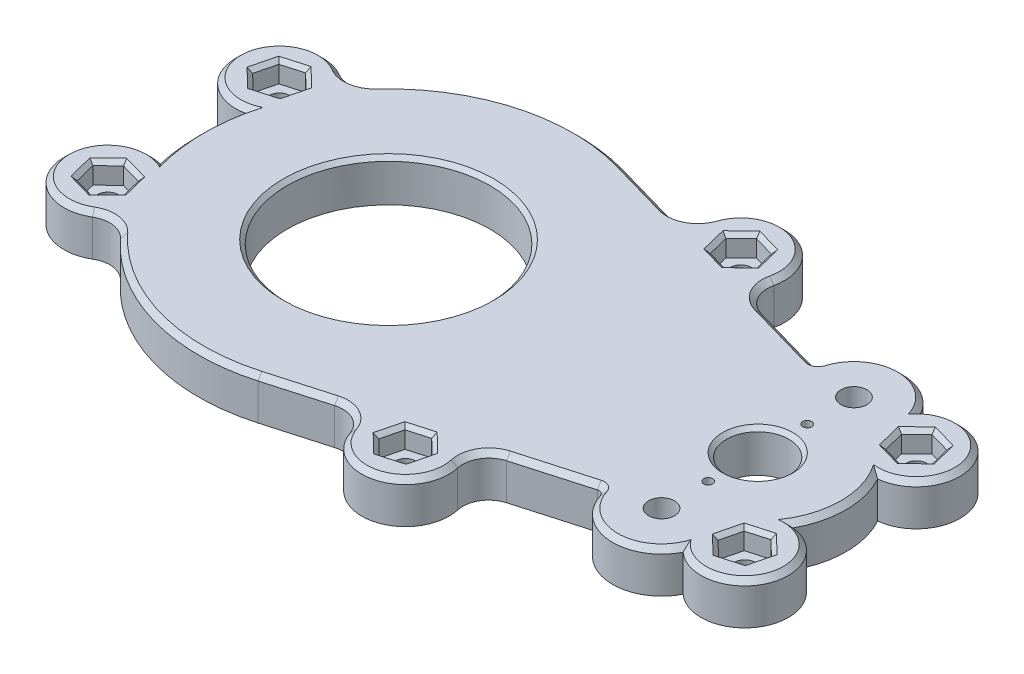
SolidWorks part; units mm, degrees
ref_plane "Front Plane" through (0, 0, 0) normal (0, 0, 1) x (1, 0, 0)
ref_plane "Top Plane" through (0, 0, 0) normal (0, 1, 0) x (1, 0, 0)
ref_plane "Right Plane" through (0, 0, 0) normal (1, 0, 0) x (0, 0, -1)
sketch "Sketch1" plane through (0, 0, 0) normal (0, 1, 0) x (1, 0, 0)
  line L0 (0, 73.0538) -> (0, -65.1274) construction
  line L1 (35.5, 6.365) -> (-28.5632, 24.502) construction
  line L2 (-70.6215, 0) -> (67.3742, 0) construction
  line L3 (35.5, -6.365) -> (-28.5632, -24.502) construction
  line L4 (4.5177, -15.1364) -> (0.1592, 0.2585)
  line L5 (0.1592, 0.2585) -> (4.6815, 1.5388)
  line L6 (4.6815, 1.5388) -> (9.04, -13.8561)
  line L7 (9.04, -13.8561) -> (9.5848, -15.7805)
  line L8 (9.5848, -15.7805) -> (5.0625, -17.0608)
  line L9 (5.0625, -17.0608) -> (4.5177, -15.1364)
  line L10 (-35.5, 0) -> (-60.5, 0) construction
  line L11 (-35.5, 0) -> (-35.5, 25) construction
  line L13 (-100, -75) -> (100, -75)
  line L14 (-100, -75) -> (-100, 75)
  line L15 (-100, 75) -> (100, 75)
  line L16 (100, -75) -> (100, 75)
  line L17 (-100, -75) -> (100, 75) construction
  line L18 (-100, 75) -> (100, -75) construction
  circle A0 centre (35.5, 0) radius 6
  circle A1 centre (-35.5, 0) radius 13.5
  circle A2 centre (-35.5, 0) radius 25.465 construction
  circle A3 centre (35.5, 0) radius 6.365 construction
  circle A4 centre (-60.5, 0) radius 2
  circle A5 centre (-35.5, 25) radius 2
  circle A6 centre (-10.5, 0) radius 2
  circle A7 centre (-35.5, -25) radius 2
  circle A8 centre (35.5, 18.5) radius 2.5
  circle A9 centre (35.5, -18.5) radius 2.5
  point P35 (0, 0)
  dimension "D1" = 12
  dimension "D2" = 27
  dimension "D5" = 50.93
  dimension "D6" = 12.73
  dimension "D12" = 4
  dimension "D19" = 5
  dimension "D3" = 71
  dimension "D4" = 35.5
  dimension "D7" = 90
  dimension "D8" = 27.5
  dimension "D9" = 4.7
  dimension "D10" = 16
  dimension "D11" = 2
  dimension "D13" = 25
  dimension "D15" = 90
  dimension "D16" = 25
  dimension "D17" = 200
  dimension "D18" = 150
  dimension "D20" = 18.5
  dimension "D14" = 4
extrude "Boss-Extrude1" add sketch "Sketch1" along normal blind 4
sketch "Sketch3" plane through (0, 4, 0) normal (0, 1, 0) x (1, 0, 0)
  line L0 (-26.5739, 31.2502) -> (39.0704, 12.5001)
  line L1 (-100, -75) -> (100, -75)
  line L2 (-100, -75) -> (-100, 75)
  line L3 (-100, 75) -> (100, 75)
  line L4 (100, -75) -> (100, 75)
  line L5 (-35.5, 0) -> (35.5, 0) construction
  line L6 (-26.5739, -31.2502) -> (39.0704, -12.5001)
  arc A0 (-26.5739, 31.2502) -> (-26.5739, -31.2502) centre (-35.5, 0) ccw
  arc A1 (39.0704, -12.5001) -> (39.0704, 12.5001) centre (35.5, 0) ccw
  dimension "D1" = 65
  dimension "D2" = 26
extrude "Boss-Extrude2" add sketch "Sketch3" along normal blind 8.25
sketch "Sketch6" plane through (0, 12.25, 0) normal (0, 1, 0) x (1, 0, 0)
  circle A0 centre (35.5, 18.5) radius 5.4
  circle A1 centre (35.5, -18.5) radius 5.4
  dimension "D1" = 10.8
extrude "Cut-Extrude2" cut sketch "Sketch6" against normal up to surface (8.25 mm away) up to face at (-35.5, 4, 27)
fillet "Fillet1" radius 2.5 4 edges at (9.5848, 2, 15.7805) (5.0625, 2, 17.0608) (4.6815, 2, -1.5388) (0.1592, 2, -0.2585)
fillet "Fillet2" radius 5 4 edges at (36.5847, 8.125, 13.2101) (31.7849, 8.125, 14.5811) (36.5847, 8.125, -13.2101) (31.7849, 8.125, -14.5811)
sketch "Sketch2" plane through (0, 4, 0) normal (0, 1, 0) x (1, 0, 0)
  line L0 (29.5, 0) -> (41.5, 0) construction
  line L1 (35.5, 0) -> (35.5, -6) construction
  line L2 (35.5, 0) -> (35.5, 6) construction
  circle A0 centre (-35.5, 25) radius 4.4
  circle A1 centre (-10.5, 0) radius 4.4
  circle A2 centre (-35.5, -25) radius 4.4
  circle A3 centre (-60.5, 0) radius 4.4
  circle A4 centre (35.5, 0) radius 6 construction
  circle A7 centre (35.5, 18.5) radius 5.4
  circle A8 centre (35.5, -18.5) radius 5.4
  arc A9 (40.6003, 16.7261) -> (30.3389, 20.0883) centre (35.5, 18.5) ccw construction
  dimension "D1" = 8.8
extrude "Cut-Extrude1" cut sketch "Sketch2" against normal blind 2
sketch "Sketch8" plane through (0, 0, 0) normal (0, -1, 0) x (1, 0, 0)
  line L0 (-35.5, 0) -> (-100, 0) construction
  line L1 (-100, -75) -> (-100, 75) construction
  line L2 (-35.5, 0) -> (100, 0) construction
  line L3 (100, 75) -> (100, -75) construction
  line L4 (49.5, 21.4955) -> (49.5, -20.5045) construction
  line L5 (0, 32.8542) -> (0, -34.16) construction
  line L6 (-73, 27.0496) -> (-73, -26.9504) construction
  line L11 (-26.5739, -31.2502) -> (24.1868, -16.7513)
  line L12 (24.1868, 16.7513) -> (-26.5739, 31.2502)
  line L13 (-26.5739, -31.2502) -> (24.1868, -16.7513) construction
  line L14 (24.1868, 16.7513) -> (-26.5739, 31.2502) construction
  circle A0 centre (-35.5, 0) radius 32.5 construction
  arc A1 (-26.5739, 31.2502) -> (-26.5739, -31.2502) centre (-35.5, 0) ccw construction
  circle A13 centre (49.5, 16.5) radius 2
  circle A14 centre (-73, 16.5) radius 2
  circle A15 centre (0, 32.25) radius 2
  circle A16 centre (49.5, 16.5) radius 4.4 construction
  circle A17 centre (0, 32.25) radius 4.4 construction
  circle A18 centre (-73, 16.5) radius 4.4 construction
  circle A19 centre (35.5, 18.5) radius 5.4 construction
  arc A20 (40.6003, 16.7261) -> (30.3389, 20.0883) centre (35.5, 18.5) ccw construction
  circle A21 centre (35.5, -18.5) radius 5.4 construction
  circle A22 centre (-73, -16.5) radius 4.4 construction
  circle A23 centre (-73, -16.5) radius 2
  circle A24 centre (0, -32.25) radius 4.4 construction
  circle A25 centre (0, -32.25) radius 2
  circle A26 centre (49.5, -16.5) radius 4.4 construction
  circle A27 centre (49.5, -16.5) radius 2
  circle A28 centre (49.5, 16.5) radius 8.4 construction
  circle A29 centre (0, 32.25) radius 8.4 construction
  circle A30 centre (-73, 16.5) radius 8.4 construction
  arc A44 (30.3389, -20.0883) -> (40.6003, -16.7261) centre (35.5, -18.5) ccw
  arc A45 (42.5943, -10.8936) -> (40.6003, -16.7261) centre (45.3228, -15.0835) ccw
  arc A46 (42.5943, -10.8936) -> (42.5943, 10.8936) centre (35.5, 0) ccw
  arc A47 (40.6003, 16.7261) -> (42.5943, 10.8936) centre (45.3228, 15.0835) ccw
  arc A48 (30.3389, -20.0883) -> (24.1868, -16.7513) centre (25.5601, -21.559) ccw
  arc A49 (40.6003, 16.7261) -> (30.3389, 20.0883) centre (35.5, 18.5) ccw
  arc A50 (24.1868, 16.7513) -> (30.3389, 20.0883) centre (25.5601, 21.559) ccw
  arc A51 (-26.5739, 31.2502) -> (-26.5739, -31.2502) centre (-35.5, 0) ccw
  arc A52 (30.3389, -20.0883) -> (40.6003, -16.7261) centre (35.5, -18.5) ccw construction
  arc A53 (42.5943, -10.8936) -> (40.6003, -16.7261) centre (45.3228, -15.0835) ccw construction
  arc A54 (42.5943, -10.8936) -> (42.5943, 10.8936) centre (35.5, 0) ccw construction
  arc A55 (40.6003, 16.7261) -> (42.5943, 10.8936) centre (45.3228, 15.0835) ccw construction
  arc A56 (30.3389, -20.0883) -> (24.1868, -16.7513) centre (25.5601, -21.559) ccw construction
  arc A57 (40.6003, 16.7261) -> (30.3389, 20.0883) centre (35.5, 18.5) ccw construction
  arc A58 (24.1868, 16.7513) -> (30.3389, 20.0883) centre (25.5601, 21.559) ccw construction
  arc A59 (-26.5739, 31.2502) -> (-26.5739, -31.2502) centre (-35.5, 0) ccw construction
  dimension "D1" = 0
  dimension "D2" = 4
  dimension "D4" = 33
  dimension "D5" = 49.5
  dimension "D3" = 8.8
  dimension "D8" = 16.8
  dimension "D6" = 64.5
  dimension "D7" = 73
extrude "Cut-Extrude3" cut sketch "Sketch8" against normal through all both and the other way through all
sketch "Sketch13" plane through (0, 12.25, 0) normal (0, 1, 0) x (1, 0, 0)
  line L0 (-100, 0) -> (100, 0) construction
  line L1 (-100, 75) -> (-100, -75) construction
  line L2 (100, -75) -> (100, 75) construction
  line L3 (57.9, 16.5) -> (57.9, -16.5) construction
  line L5 (-8.1313, 30.1424) -> (-25.4754, 35.0964)
  line L6 (5.7914, -26.1656) -> (25.2854, -20.5975)
  line L7 (-25.4754, -35.0964) -> (25.2854, -20.5975)
  line L8 (25.2854, 20.5975) -> (-25.4754, 35.0964)
  line L9 (-25.4754, -35.0964) -> (-8.1313, -30.1424)
  line L10 (25.2854, 20.5975) -> (5.7914, 26.1656)
  arc A0 (5.7914, 26.1656) -> (-8.1313, 30.1424) centre (0, 32.25) ccw
  arc A1 (50.4188, 8.1504) -> (43.8854, 22.7479) centre (49.5, 16.5) ccw
  arc A2 (-65.6518, 20.5699) -> (-71.0361, 8.3328) centre (-73, 16.5) ccw
  arc A3 (-65.6518, -20.5699) -> (-71.0361, -8.3328) centre (-73, -16.5) cw
  arc A4 (5.7914, -26.1656) -> (-8.1313, -30.1424) centre (0, -32.25) cw
  arc A5 (50.4188, -8.1504) -> (43.8854, -22.7479) centre (49.5, -16.5) cw
  arc A14 (-71.0361, 8.3328) -> (-71.0361, -8.3328) centre (-35.5, 0) ccw
  arc A15 (-65.6518, -20.5699) -> (-25.4754, -35.0964) centre (-35.5, 0) ccw
  arc A22 (44.3783, 15.412) -> (26.5158, 21.2649) centre (35.5, 18.5) ccw
  arc A23 (44.3783, 15.412) -> (44.7771, 14.2455) centre (45.3228, 15.0835) ccw
  arc A24 (44.7771, -14.2455) -> (44.7771, 14.2455) centre (35.5, 0) ccw
  arc A25 (44.7771, -14.2455) -> (44.3783, -15.412) centre (45.3228, -15.0835) ccw
  arc A26 (26.5158, -21.2649) -> (44.3783, -15.412) centre (35.5, -18.5) ccw
  arc A27 (26.5158, -21.2649) -> (25.2854, -20.5975) centre (25.5601, -21.559) ccw
  arc A28 (-25.4754, 35.0964) -> (-25.4754, -35.0964) centre (-35.5, 0) ccw
  arc A29 (25.2854, 20.5975) -> (26.5158, 21.2649) centre (25.5601, 21.559) ccw
  arc A30 (43.8854, 22.7479) -> (26.5158, 21.2649) centre (35.5, 18.5) ccw
  arc A32 (50.4188, -8.1504) -> (50.4188, 8.1504) centre (35.5, 0) ccw
  arc A34 (26.5158, -21.2649) -> (43.8854, -22.7479) centre (35.5, -18.5) ccw
  arc A35 (26.5158, -21.2649) -> (25.2854, -20.5975) centre (25.5601, -21.559) ccw
  arc A36 (-25.4754, 35.0964) -> (-65.6518, 20.5699) centre (-35.5, 0) ccw
  arc A37 (25.2854, 20.5975) -> (26.5158, 21.2649) centre (25.5601, 21.559) ccw
  dimension "D1" = 16.8
  dimension "D2" = 4
extrude "Cut-Extrude6" cut sketch "Sketch13" against normal through all both and the other way through all flip side to cut
fillet "Fillet4" radius 5 6 edges at (-65.6518, 6.125, 20.5699) (-65.6518, 6.125, -20.5699) (-8.1313, 6.125, -30.1424) (5.7914, 6.125, -26.1656) (5.7914, 6.125, 26.1656) (-8.1313, 6.125, 30.1424)
sketch "Sketch16" plane through (0, 12.25, 0) normal (0, 1, 0) x (1, 0, 0)
  line L12 (-25.4754, -35.0964) -> (-14.035, -31.8287)
  line L13 (11.6951, -24.4793) -> (25.2854, -20.5975)
  line L14 (25.2854, 20.5975) -> (11.6951, 24.4793)
  line L15 (-14.035, 31.8287) -> (-25.4754, 35.0964)
  line L16 (-25.4754, -35.0964) -> (-14.035, -31.8287)
  line L17 (11.6951, -24.4793) -> (25.2854, -20.5975)
  line L18 (25.2854, 20.5975) -> (11.6951, 24.4793)
  line L19 (-14.035, 31.8287) -> (-25.4754, 35.0964)
  arc A60 (-71.0361, 8.3328) -> (-71.0361, -8.3328) centre (-35.5, 0) ccw
  arc A61 (-71.0361, -8.3328) -> (-68.692, -23.7112) centre (-73, -16.5) ccw
  arc A62 (-62.4376, -24.6296) -> (-68.692, -23.7112) centre (-66.1277, -28.0035) ccw
  arc A63 (-62.4376, -24.6296) -> (-25.4754, -35.0964) centre (-35.5, 0) ccw
  arc A64 (-7.9372, -34.9997) -> (-14.035, -31.8287) centre (-12.6617, -36.6364) ccw
  arc A65 (-7.9372, -34.9997) -> (8.1921, -30.3926) centre (0, -32.25) ccw
  arc A66 (11.6951, -24.4793) -> (8.1921, -30.3926) centre (13.0683, -29.2871) ccw
  arc A67 (26.5158, -21.2649) -> (25.2854, -20.5975) centre (25.5601, -21.559) ccw
  arc A68 (26.5158, -21.2649) -> (43.8854, -22.7479) centre (35.5, -18.5) ccw
  arc A69 (43.8854, -22.7479) -> (50.4188, -8.1504) centre (49.5, -16.5) ccw
  arc A70 (50.4188, -8.1504) -> (50.4188, 8.1504) centre (35.5, 0) ccw
  arc A71 (50.4188, 8.1504) -> (43.8854, 22.7479) centre (49.5, 16.5) ccw
  arc A72 (43.8854, 22.7479) -> (26.5158, 21.2649) centre (35.5, 18.5) ccw
  arc A73 (25.2854, 20.5975) -> (26.5158, 21.2649) centre (25.5601, 21.559) ccw
  arc A74 (8.1921, 30.3926) -> (11.6951, 24.4793) centre (13.0683, 29.2871) ccw
  arc A75 (8.1921, 30.3926) -> (-7.9372, 34.9997) centre (0, 32.25) ccw
  arc A76 (-14.035, 31.8287) -> (-7.9372, 34.9997) centre (-12.6617, 36.6364) ccw
  arc A77 (-25.4754, 35.0964) -> (-62.4376, 24.6296) centre (-35.5, 0) ccw
  arc A78 (-68.692, 23.7112) -> (-62.4376, 24.6296) centre (-66.1277, 28.0035) ccw
  arc A79 (-68.692, 23.7112) -> (-71.0361, 8.3328) centre (-73, 16.5) ccw
  arc A80 (-71.0361, 8.3328) -> (-71.0361, -8.3328) centre (-35.5, 0) ccw
  arc A81 (-71.0361, -8.3328) -> (-68.692, -23.7112) centre (-73, -16.5) ccw
  arc A82 (-62.4376, -24.6296) -> (-68.692, -23.7112) centre (-66.1277, -28.0035) ccw
  arc A83 (-62.4376, -24.6296) -> (-25.4754, -35.0964) centre (-35.5, 0) ccw
  arc A84 (-7.9372, -34.9997) -> (-14.035, -31.8287) centre (-12.6617, -36.6364) ccw
  arc A85 (-7.9372, -34.9997) -> (8.1921, -30.3926) centre (0, -32.25) ccw
  arc A86 (11.6951, -24.4793) -> (8.1921, -30.3926) centre (13.0683, -29.2871) ccw
  arc A87 (26.5158, -21.2649) -> (25.2854, -20.5975) centre (25.5601, -21.559) ccw
  arc A88 (26.5158, -21.2649) -> (43.8854, -22.7479) centre (35.5, -18.5) ccw
  arc A89 (43.8854, -22.7479) -> (50.4188, -8.1504) centre (49.5, -16.5) ccw
  arc A90 (50.4188, -8.1504) -> (50.4188, 8.1504) centre (35.5, 0) ccw
  arc A91 (50.4188, 8.1504) -> (43.8854, 22.7479) centre (49.5, 16.5) ccw
  arc A92 (43.8854, 22.7479) -> (26.5158, 21.2649) centre (35.5, 18.5) ccw
  arc A93 (25.2854, 20.5975) -> (26.5158, 21.2649) centre (25.5601, 21.559) ccw
  arc A94 (8.1921, 30.3926) -> (11.6951, 24.4793) centre (13.0683, 29.2871) ccw
  arc A95 (8.1921, 30.3926) -> (-7.9372, 34.9997) centre (0, 32.25) ccw
  arc A96 (-14.035, 31.8287) -> (-7.9372, 34.9997) centre (-12.6617, 36.6364) ccw
  arc A97 (-25.4754, 35.0964) -> (-62.4376, 24.6296) centre (-35.5, 0) ccw
  arc A98 (-68.692, 23.7112) -> (-62.4376, 24.6296) centre (-66.1277, 28.0035) ccw
  arc A99 (-68.692, 23.7112) -> (-71.0361, 8.3328) centre (-73, 16.5) ccw
  dimension "D1" = 0
extrude "Cut-Extrude7" cut sketch "Sketch16" against normal up to surface (10.25 mm away) up to face at (-35.5, 2, -23)
sketch "Sketch17" plane through (0, 0, 0) normal (0, -1, 0) x (1, 0, 0)
  line L4 (4.3815, 14.6553) -> (0.8403, 2.1469)
  line L5 (5.3625, 0.8666) -> (8.9038, 13.375)
  line L6 (4.3815, 14.6553) -> (0.8403, 2.1469)
  line L7 (5.3625, 0.8666) -> (8.9038, 13.375)
  circle A6 centre (-10.5, 0) radius 2
  circle A7 centre (-10.5, 0) radius 2
  arc A8 (2.4216, -0.8943) -> (5.3625, 0.8666) centre (2.9571, 1.5477) ccw
  arc A9 (0.8403, 2.1469) -> (2.4216, -0.8943) centre (3.2457, 1.4659) ccw
  arc A10 (8.9038, 13.375) -> (7.3224, 16.4163) centre (6.4983, 14.056) ccw
  arc A11 (7.3224, 16.4163) -> (4.3815, 14.6553) centre (6.787, 13.9743) ccw
  arc A12 (2.4216, -0.8943) -> (5.3625, 0.8666) centre (2.9571, 1.5477) ccw
  arc A13 (0.8403, 2.1469) -> (2.4216, -0.8943) centre (3.2457, 1.4659) ccw
  arc A14 (8.9038, 13.375) -> (7.3224, 16.4163) centre (6.4983, 14.056) ccw
  arc A15 (7.3224, 16.4163) -> (4.3815, 14.6553) centre (6.787, 13.9743) ccw
  circle A17 centre (-35.5, -25) radius 2
  circle A18 centre (-35.5, -25) radius 2
  circle A20 centre (-35.5, 25) radius 2
  circle A21 centre (-35.5, 25) radius 2
  circle A23 centre (-60.5, 0) radius 2
  circle A24 centre (-60.5, 0) radius 2
  dimension "D1" = 0
  dimension "D2" = 0
  dimension "D3" = 0
  dimension "D4" = 0
  dimension "D5" = 0
extrude "Boss-Extrude3" add sketch "Sketch17" against normal up to surface (2 mm away) up to face at (35.5, 2, -16)
sketch "Sketch18" plane through (0, 2, 0) normal (0, 1, 0) x (1, 0, 0)
  line L8 (-25.4754, -35.0964) -> (-14.035, -31.8287)
  line L9 (11.6951, -24.4793) -> (25.2854, -20.5975)
  line L10 (25.2854, 20.5975) -> (11.6951, 24.4793)
  line L11 (-14.035, 31.8287) -> (-25.4754, 35.0964)
  line L12 (-25.4754, -35.0964) -> (-14.035, -31.8287)
  line L13 (11.6951, -24.4793) -> (25.2854, -20.5975)
  line L14 (25.2854, 20.5975) -> (11.6951, 24.4793)
  line L15 (-14.035, 31.8287) -> (-25.4754, 35.0964)
  circle A20 centre (-35.5, 0) radius 13.5
  circle A21 centre (0, 32.25) radius 2
  circle A22 centre (-73, 16.5) radius 2
  circle A23 centre (-73, -16.5) radius 2
  circle A24 centre (0, 32.25) radius 2 construction
  circle A25 centre (-35.5, 0) radius 13.5 construction
  circle A26 centre (0, -32.25) radius 2
  circle A27 centre (35.5, -18.5) radius 2.5
  circle A28 centre (35.5, 0) radius 6
  circle A29 centre (49.5, -16.5) radius 2
  circle A30 centre (35.5, 18.5) radius 2.5
  circle A31 centre (49.5, 16.5) radius 2
  circle A32 centre (-73, 16.5) radius 2 construction
  circle A33 centre (-73, -16.5) radius 2 construction
  circle A34 centre (0, -32.25) radius 2 construction
  circle A35 centre (35.5, -18.5) radius 2.5 construction
  circle A36 centre (35.5, 0) radius 6 construction
  circle A37 centre (35.5, 18.5) radius 2.5 construction
  circle A38 centre (49.5, 16.5) radius 2 construction
  circle A39 centre (49.5, -16.5) radius 2 construction
  arc A40 (-68.692, 23.7112) -> (-71.0361, 8.3328) centre (-73, 16.5) ccw
  arc A41 (-71.0361, 8.3328) -> (-71.0361, -8.3328) centre (-35.5, 0) ccw
  arc A42 (-71.0361, -8.3328) -> (-68.692, -23.7112) centre (-73, -16.5) ccw
  arc A43 (-62.4376, -24.6296) -> (-68.692, -23.7112) centre (-66.1277, -28.0035) ccw
  arc A44 (-62.4376, -24.6296) -> (-25.4754, -35.0964) centre (-35.5, 0) ccw
  arc A45 (-7.9372, -34.9997) -> (-14.035, -31.8287) centre (-12.6617, -36.6364) ccw
  arc A46 (-7.9372, -34.9997) -> (8.1921, -30.3926) centre (0, -32.25) ccw
  arc A47 (11.6951, -24.4793) -> (8.1921, -30.3926) centre (13.0683, -29.2871) ccw
  arc A48 (26.5158, -21.2649) -> (25.2854, -20.5975) centre (25.5601, -21.559) ccw
  arc A49 (26.5158, -21.2649) -> (43.8854, -22.7479) centre (35.5, -18.5) ccw
  arc A50 (43.8854, -22.7479) -> (50.4188, -8.1504) centre (49.5, -16.5) ccw
  arc A51 (50.4188, -8.1504) -> (50.4188, 8.1504) centre (35.5, 0) ccw
  arc A52 (50.4188, 8.1504) -> (43.8854, 22.7479) centre (49.5, 16.5) ccw
  arc A53 (43.8854, 22.7479) -> (26.5158, 21.2649) centre (35.5, 18.5) ccw
  arc A54 (25.2854, 20.5975) -> (26.5158, 21.2649) centre (25.5601, 21.559) ccw
  arc A55 (8.1921, 30.3926) -> (11.6951, 24.4793) centre (13.0683, 29.2871) ccw
  arc A56 (8.1921, 30.3926) -> (-7.9372, 34.9997) centre (0, 32.25) ccw
  arc A57 (-14.035, 31.8287) -> (-7.9372, 34.9997) centre (-12.6617, 36.6364) ccw
  arc A58 (-25.4754, 35.0964) -> (-62.4376, 24.6296) centre (-35.5, 0) ccw
  arc A59 (-68.692, 23.7112) -> (-62.4376, 24.6296) centre (-66.1277, 28.0035) ccw
  arc A60 (-68.692, 23.7112) -> (-71.0361, 8.3328) centre (-73, 16.5) ccw
  arc A61 (-71.0361, 8.3328) -> (-71.0361, -8.3328) centre (-35.5, 0) ccw
  arc A62 (-71.0361, -8.3328) -> (-68.692, -23.7112) centre (-73, -16.5) ccw
  arc A63 (-62.4376, -24.6296) -> (-68.692, -23.7112) centre (-66.1277, -28.0035) ccw
  arc A64 (-62.4376, -24.6296) -> (-25.4754, -35.0964) centre (-35.5, 0) ccw
  arc A65 (-7.9372, -34.9997) -> (-14.035, -31.8287) centre (-12.6617, -36.6364) ccw
  arc A66 (-7.9372, -34.9997) -> (8.1921, -30.3926) centre (0, -32.25) ccw
  arc A67 (11.6951, -24.4793) -> (8.1921, -30.3926) centre (13.0683, -29.2871) ccw
  arc A68 (26.5158, -21.2649) -> (25.2854, -20.5975) centre (25.5601, -21.559) ccw
  arc A69 (26.5158, -21.2649) -> (43.8854, -22.7479) centre (35.5, -18.5) ccw
  arc A70 (43.8854, -22.7479) -> (50.4188, -8.1504) centre (49.5, -16.5) ccw
  arc A71 (50.4188, -8.1504) -> (50.4188, 8.1504) centre (35.5, 0) ccw
  arc A72 (50.4188, 8.1504) -> (43.8854, 22.7479) centre (49.5, 16.5) ccw
  arc A73 (43.8854, 22.7479) -> (26.5158, 21.2649) centre (35.5, 18.5) ccw
  arc A74 (25.2854, 20.5975) -> (26.5158, 21.2649) centre (25.5601, 21.559) ccw
  arc A75 (8.1921, 30.3926) -> (11.6951, 24.4793) centre (13.0683, 29.2871) ccw
  arc A76 (8.1921, 30.3926) -> (-7.9372, 34.9997) centre (0, 32.25) ccw
  arc A77 (-14.035, 31.8287) -> (-7.9372, 34.9997) centre (-12.6617, 36.6364) ccw
  arc A78 (-25.4754, 35.0964) -> (-62.4376, 24.6296) centre (-35.5, 0) ccw
  arc A79 (-68.692, 23.7112) -> (-62.4376, 24.6296) centre (-66.1277, 28.0035) ccw
  dimension "D1" = 0
extrude "Boss-Extrude4" add sketch "Sketch18" along normal blind 6
sketch "Sketch19" plane through (0, 0, 0) normal (0, -1, 0) x (1, 0, 0)
  line L0 (25.975, 0) -> (45.025, 0) construction
  circle A0 centre (-35.5, 0) radius 19.5
  circle A1 centre (35.5, 0) radius 9.525 construction
  circle A2 centre (35.5, 9.525) radius 0.875
  circle A3 centre (35.5, -9.525) radius 0.875
  dimension "D1" = 39
  dimension "D2" = 19.05
  dimension "D3" = 1.75
extrude "Cut-Extrude8" cut sketch "Sketch19" against normal through all both and the other way through all
sketch "Sketch20" plane through (0, 0, 0) normal (0, -1, 0) x (1, 0, 0)
  line L1 (40.292, 18.5) -> (37.896, 22.65)
  line L2 (37.896, 22.65) -> (33.104, 22.65)
  line L3 (33.104, 22.65) -> (30.708, 18.5)
  line L4 (30.708, 18.5) -> (33.104, 14.35)
  line L5 (33.104, 14.35) -> (37.896, 14.35)
  line L6 (37.896, 14.35) -> (40.292, 18.5)
  line L7 (40.292, -18.5) -> (37.896, -14.35)
  line L8 (37.896, -14.35) -> (33.104, -14.35)
  line L9 (33.104, -14.35) -> (30.708, -18.5)
  line L10 (30.708, -18.5) -> (33.104, -22.65)
  line L11 (33.104, -22.65) -> (37.896, -22.65)
  line L12 (37.896, -22.65) -> (40.292, -18.5)
  circle A0 centre (35.5, 18.5) radius 4.15 construction
  circle A1 centre (35.5, -18.5) radius 4.15 construction
  dimension "D1" = 8.3
  dimension "D2" = 8.3
extrude "Cut-Extrude9" cut sketch "Sketch20" against normal blind 4
sketch "Sketch21" plane through (0, 8, 0) normal (0, 1, 0) x (1, 0, 0)
  line L0 (25.2854, 20.5975) -> (11.6951, 24.4793) construction
  line L1 (-70.0127, 13.6093) -> (-69.0029, 17.6417)
  line L2 (-69.0029, 17.6417) -> (-71.9902, 20.5324)
  line L3 (-71.9902, 20.5324) -> (-75.9873, 19.3907)
  line L4 (-75.9873, 19.3907) -> (-76.9971, 15.3583)
  line L5 (-76.9971, 15.3583) -> (-74.0098, 12.4676)
  line L6 (-74.0098, 12.4676) -> (-70.0127, 13.6093)
  line L7 (-70.0127, -13.6093) -> (-74.0098, -12.4676)
  line L8 (-74.0098, -12.4676) -> (-76.9971, -15.3583)
  line L9 (-76.9971, -15.3583) -> (-75.9873, -19.3907)
  line L10 (-75.9873, -19.3907) -> (-71.9902, -20.5324)
  line L11 (-71.9902, -20.5324) -> (-69.0029, -17.6417)
  line L12 (-69.0029, -17.6417) -> (-70.0127, -13.6093)
  line L13 (3.9971, 31.1083) -> (2.9873, 35.1407)
  line L14 (2.9873, 35.1407) -> (-1.0098, 36.2824)
  line L15 (-1.0098, 36.2824) -> (-3.9971, 33.3917)
  line L16 (-3.9971, 33.3917) -> (-2.9873, 29.3593)
  line L17 (-2.9873, 29.3593) -> (1.0098, 28.2176)
  line L18 (1.0098, 28.2176) -> (3.9971, 31.1083)
  line L19 (50.5098, 12.4676) -> (53.4971, 15.3583)
  line L20 (53.4971, 15.3583) -> (52.4873, 19.3907)
  line L21 (52.4873, 19.3907) -> (48.4902, 20.5324)
  line L22 (48.4902, 20.5324) -> (45.5029, 17.6417)
  line L23 (45.5029, 17.6417) -> (46.5127, 13.6093)
  line L24 (46.5127, 13.6093) -> (50.5098, 12.4676)
  line L25 (53.4971, -15.3583) -> (50.5098, -12.4676)
  line L26 (50.5098, -12.4676) -> (46.5127, -13.6093)
  line L27 (46.5127, -13.6093) -> (45.5029, -17.6417)
  line L28 (45.5029, -17.6417) -> (48.4902, -20.5324)
  line L29 (48.4902, -20.5324) -> (52.4873, -19.3907)
  line L30 (52.4873, -19.3907) -> (53.4971, -15.3583)
  line L31 (3.9971, -31.1083) -> (1.0098, -28.2176)
  line L32 (1.0098, -28.2176) -> (-2.9873, -29.3593)
  line L33 (-2.9873, -29.3593) -> (-3.9971, -33.3917)
  line L34 (-3.9971, -33.3917) -> (-1.0098, -36.2824)
  line L35 (-1.0098, -36.2824) -> (2.9873, -35.1407)
  line L36 (2.9873, -35.1407) -> (3.9971, -31.1083)
  line L37 (11.6951, -24.4793) -> (25.2854, -20.5975) construction
  line L38 (-25.4754, -35.0964) -> (-14.035, -31.8287) construction
  line L39 (-14.035, 31.8287) -> (-25.4754, 35.0964) construction
  circle A0 centre (-73, 16.5) radius 3.6 construction
  circle A1 centre (-73, -16.5) radius 3.6 construction
  circle A2 centre (0, 32.25) radius 3.6 construction
  circle A3 centre (49.5, 16.5) radius 3.6 construction
  circle A4 centre (49.5, -16.5) radius 3.6 construction
  circle A5 centre (0, -32.25) radius 3.6 construction
  point P46 (-70.4966, -19.087)
  dimension "D1" = 7.2
  dimension "D2" = 7.2
  dimension "D3" = 7.2
  dimension "D4" = 7.2
  dimension "D5" = 7.2
  dimension "D6" = 7.2
extrude "Cut-Extrude10" cut sketch "Sketch21" against normal blind 4
chamfer "Chamfer1" distance 1 angle 45 24 edges at (-45.4449, 8, -35.1191) (-19.7552, 8, -33.4625) (-10.3549, 8, -32.2003) (2.307, 8, -40.327) (8.7665, 8, -26.7387) (18.4902, 8, -22.5384) (26.0369, 8, -20.68) (34.7003, 8, -27.8659) (57.1671, 8, -19.9316) (52.5, 8, 0) (57.1671, 8, 19.9316) (34.7003, 8, 27.8659) (26.0369, 8, 20.68) (18.4902, 8, 22.5384) (8.7665, 8, 26.7387) (2.307, 8, 40.327) (-10.3549, 8, 32.2003) (-19.7552, 8, 33.4625) (-45.4449, 8, 35.1191) (-65.4012, 8, 23.0566) (-81.3041, 8, 17.7658) (-72, 8, 0) (-81.3041, 8, -17.7658) (-65.4012, 8, -23.0566)
chamfer "Chamfer2" distance 0.75 angle 45 38 edges at (35.5, 8, 6) (-35.5, 8, -19.5) (46.9966, 8, -19.087) (50.4887, 8, -19.9616) (52.9922, 8, -17.3745) (52.0034, 8, -13.913) (46.0078, 8, -15.6255) (48.5113, 8, -13.0384) (3.4922, 8, -33.1245) (0.9887, 8, -35.7116) (-2.5034, 8, -34.837) (-3.4922, 8, -31.3755) (2.5034, 8, -29.663) (-0.9887, 8, -28.7884) (-69.5078, 8, -15.6255) (-70.4966, 8, -19.087) (-73.9887, 8, -19.9616) (-76.4922, 8, -17.3745) (-75.5034, 8, -13.913) (-72.0113, 8, -13.0384) (-69.5078, 8, 15.6255) (-72.0113, 8, 13.0384) (-75.5034, 8, 13.913) (-76.4922, 8, 17.3745) (-73.9887, 8, 19.9616) (-70.4966, 8, 19.087) (2.5034, 8, 29.663) (3.4922, 8, 33.1245) (0.9887, 8, 35.7116) (-2.5034, 8, 34.837) (-3.4922, 8, 31.3755) (-0.9887, 8, 28.7884) (52.0034, 8, 13.913) (48.5113, 8, 13.0384) (46.0078, 8, 15.6255) (46.9966, 8, 19.087) (52.9922, 8, 17.3745) (50.4887, 8, 19.9616)
